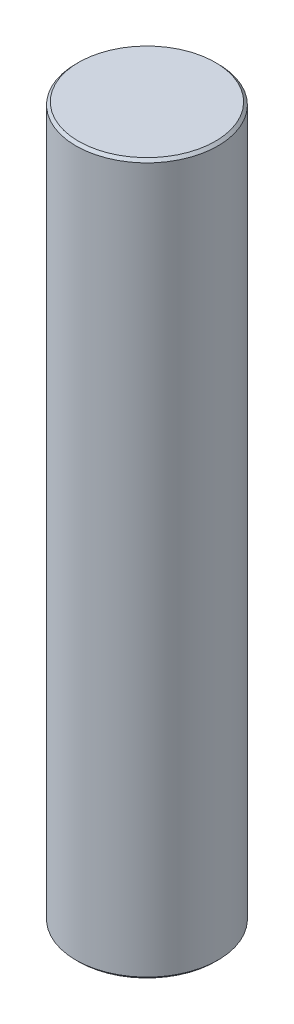
SolidWorks part; units mm, degrees
material "Ductile Iron (SN)"
ref_plane "Front Plane" through (0, 0, 0) normal (0, 0, 1) x (1, 0, 0)
ref_plane "Top Plane" through (0, 0, 0) normal (0, 1, 0) x (1, 0, 0)
ref_plane "Right Plane" through (0, 0, 0) normal (1, 0, 0) x (0, 0, -1)
sketch "Sketch1" plane through (0, 0, 0) normal (0, 1, 0) x (1, 0, 0)
  circle A0 centre (0, 0) radius 4
  dimension "D1" = 8
extrude "Boss-Extrude1" add sketch "Sketch1" along normal blind 40
chamfer "Chamfer1" distance 0.15 angle 45 2 edges at (0, 0, 4) (0, 40, 4)
